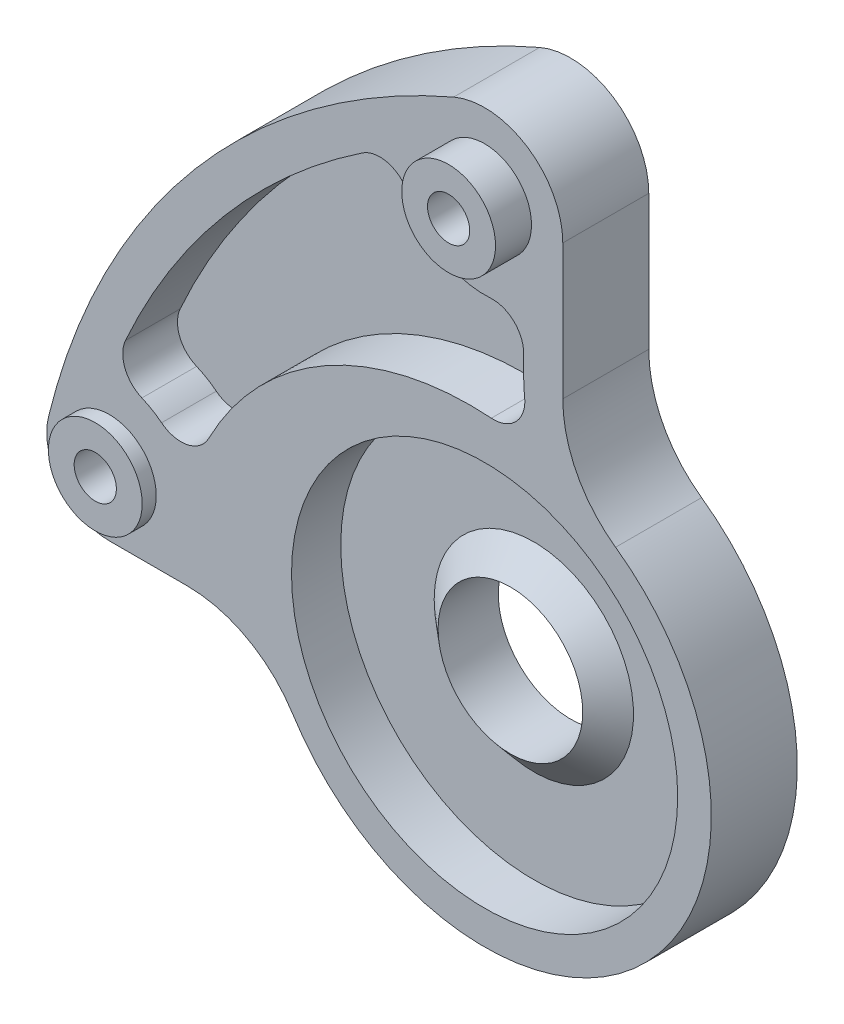
SolidWorks part; units mm, degrees
ref_plane "Front Plane" through (0, 0, 0) normal (0, 0, 1) x (1, 0, 0)
ref_plane "Top Plane" through (0, 0, 0) normal (0, 1, 0) x (1, 0, 0)
ref_plane "Right Plane" through (0, 0, 0) normal (1, 0, 0) x (0, 0, -1)
ref_plane "Plane1" through (0, 0, 5.5) normal (0, 0, 1) x (1, 0, 0)
sketch "Sketch1" plane through (0, 0, 5.5) normal (0, 0, 1) x (1, 0, 0)
  line L0 (5, 18.3644) -> (5, 27)
  line L1 (-24, -4) -> (-19.0329, -4)
  arc A0 (8.3778, 11.8348) -> (5, 18.3644) centre (13, 18.3644) cw
  arc A1 (5, 27) -> (-1.9784, 31.5919) centre (0, 27) ccw
  arc A2 (-1.9784, 31.5919) -> (-27.8856, 0.9498) centre (15.8274, -9.7355) ccw
  arc A3 (-27.8856, 0.9498) -> (-24, -4) centre (-24, 0) ccw
  arc A4 (-19.0329, -4) -> (-12.2656, -7.7333) centre (-19.0329, -12) cw
  arc A5 (-12.2656, -7.7333) -> (8.3778, 11.8348) centre (0, 0) ccw
extrude "Boss-Extrude1" add sketch "Sketch1" against normal blind 5.5
sketch "Sketch2" plane through (0, 0, 5.5) normal (0, 0, 1) x (1, 0, 0)
  circle A0 centre (0, 27) radius 3
  dimension "D1" = 6
extrude "Boss-Extrude2" add sketch "Sketch2" along normal blind 2.3
sketch "Sketch3" plane through (0, 0, 5.5) normal (0, 0, 1) x (1, 0, 0)
  circle A0 centre (-24, 0) radius 3
  dimension "D1" = 6
extrude "Boss-Extrude3" add sketch "Sketch3" along normal blind 0.9
sketch "Sketch4" plane through (0, 0, 0) normal (0, 0, -1) x (-1, 0, 0)
  circle A0 centre (0, 0) radius 4.625
  dimension "D1" = 9.25
extrude "Cut-Extrude1" cut sketch "Sketch4" against normal through all
sketch "Sketch5" plane through (0, 0, 7.8) normal (0, 0, 1) x (1, 0, 0)
  circle A0 centre (0, 27) radius 1.35
  circle A1 centre (-24, 0) radius 1.35
  dimension "D1" = 2.7
  dimension "D2" = 2.7
extrude "Cut-Extrude2" cut sketch "Sketch5" against normal through all
sketch "Sketch7" plane through (0, 0, 5.5) normal (0, 0, 1) x (1, 0, 0)
  circle A0 centre (0, 0) radius 12.35
  circle A1 centre (0, 0) radius 12.1 construction
  dimension "D1" = 0.25
  dimension "D2" = 24.2
extrude "Cut-Extrude4" cut sketch "Sketch7" against normal blind 3.15
sketch "Sketch8" plane through (0, 0, 5.5) normal (0, 0, 1) x (1, 0, 0)
  line L0 (2.5, 18.3644) -> (2.5, 19.6403)
  arc A0 (0.3644, 21.6357) -> (-4.8853, 24.7546) centre (0, 27) cw
  arc A1 (-4.8853, 24.7546) -> (-7.8152, 25.5814) centre (-6.7026, 23.9194) ccw
  arc A2 (-7.8152, 25.5814) -> (-22.9686, 7.6175) centre (15.8274, -9.7355) ccw
  arc A3 (-22.9686, 7.6175) -> (-21.9175, 4.957) centre (-21.1429, 6.8009) ccw
  arc A4 (-21.9175, 4.957) -> (-20.6588, 4.2124) centre (-24, 0) cw
  arc A5 (-20.6588, 4.2124) -> (-17.6384, 4.8627) centre (-19.4159, 5.7794) ccw
  arc A6 (-17.6384, 4.8627) -> (0.4318, 15.0138) centre (-0.9047, -3.7663) cw
  arc A7 (0.4318, 15.0138) -> (2.5619, 17.2256) centre (0.5737, 17.0087) ccw
  arc A8 (2.5619, 17.2256) -> (2.5, 18.3644) centre (13, 18.3644) cw
  arc A9 (2.5, 19.6403) -> (0.3644, 21.6357) centre (0.5, 19.6403) ccw
extrude "Cut-Extrude5" cut sketch "Sketch8" against normal blind 3.5
sketch "Sketch9" plane through (0, 0, 2.35) normal (0, 0, 1) x (1, 0, 0)
  circle A0 centre (0, 0) radius 4.625 construction
  circle A1 centre (0, 0) radius 4.625
  circle A3 centre (0, 0) radius 6.375
  dimension "D2" = 1.75
extrude "Boss-Extrude4" add sketch "Sketch9" along normal blind 1.5
chamfer "Chamfer1" distance 1.5 distance2 1.75 1 edges at (6.375, 0, 3.85) first distance on face at (6.375, 0, 3.85)
